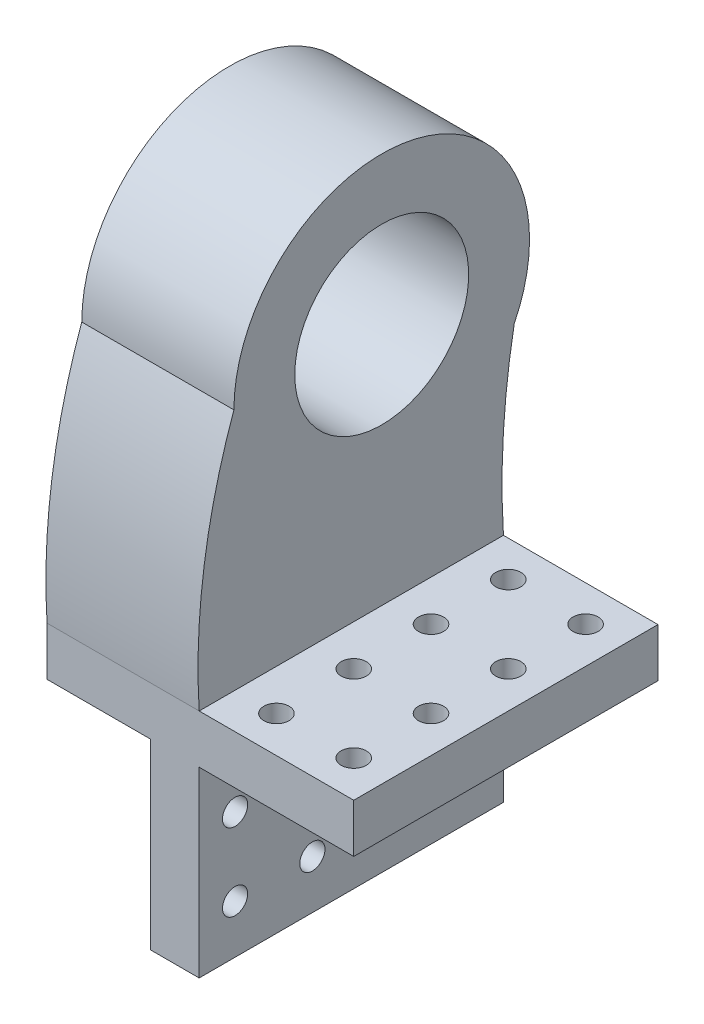
SolidWorks part; units mm, degrees
ref_plane "Alzado" through (0, 0, 0) normal (0, 0, 1) x (1, 0, 0)
ref_plane "Planta" through (0, 0, 0) normal (0, 1, 0) x (1, 0, 0)
ref_plane "Vista lateral" through (0, 0, 0) normal (1, 0, 0) x (0, 0, -1)
sketch "Croquis1" plane through (0, 0, 0) normal (0, 1, 0) x (1, 0, 0)
  line L1 (-25.2, -25) -> (25.2, -25)
  line L2 (-25.2, -25) -> (-25.2, 25)
  line L3 (-25.2, 25) -> (25.2, 25)
  line L4 (25.2, -25) -> (25.2, 25)
  line L5 (-25.2, -25) -> (25.2, 25) construction
  line L6 (-25.2, 25) -> (25.2, -25) construction
  point P0 (0, 0)
  dimension "D1" = 50.4
  dimension "D2" = 50
extrude "Saliente-Extruir1" add sketch "Croquis1" along normal blind 8
sketch "Croquis2" plane through (-25.2, 0, 0) normal (-1, 0, 0) x (0, 0, 1)
  line L0 (-25, 8) -> (25, 8) construction
  line L1 (25, 8) -> (25, 0) construction
  line L2 (-25, 8) -> (25, 8)
  circle A0 centre (-5, 48) radius 14.29
  arc A1 (19.29, 48) -> (-26.7814, 37.2494) centre (-5, 48) ccw
  arc A2 (-25, 8) -> (-26.7814, 37.2494) centre (-144.7726, 15.3844) ccw
  arc A3 (25, 8) -> (19.29, 48) centre (-74.8101, 14.1597) ccw
  dimension "D1" = 28.58
  dimension "D2" = 10
  dimension "D5" = 100
  dimension "D6" = 120
  dimension "D3" = 40
  dimension "D4" = 30
extrude "Saliente-Extruir2" add sketch "Croquis2" against normal blind 25
sketch "Croquis3" plane through (0, 0, 0) normal (0, -1, 0) x (1, 0, 0)
  line L1 (-8.2, -25) -> (-0.2, -25)
  line L2 (-8.2, -25) -> (-8.2, 25)
  line L3 (-8.2, 25) -> (-0.2, 25)
  line L4 (-0.2, -25) -> (-0.2, 25)
  line L5 (-25.2, 25) -> (25.2, 25) construction
  line L7 (25.2, 25) -> (25.2, -25) construction
  dimension "D1" = 8
  dimension "D2" = 25.4
extrude "Saliente-Extruir3" add sketch "Croquis3" along normal blind 30
sketch "Croquis4" plane through (0, 8, 0) normal (0, 1, 0) x (1, 0, 0)
  line L0 (25.2, -25) -> (25.2, 25) construction
  line L1 (-0.2, -25) -> (25.2, -25) construction
  circle A0 centre (19.2, -19) radius 2.07
  circle A1 centre (19.2, -6.3) radius 2.07
  circle A2 centre (19.2, 6.4) radius 2.07
  circle A3 centre (19.2, 19.1) radius 2.07
  circle A4 centre (6.5, 19.1) radius 2.07
  circle A5 centre (6.5, 6.4) radius 2.07
  circle A6 centre (6.5, -6.3) radius 2.07
  circle A7 centre (6.5, -19) radius 2.07
  dimension "D1" = 4.14
  dimension "D2" = 6
  dimension "D3" = 6
  dimension "D4" = 4
  dimension "D5" = 2
extrude "Cortar-Extruir1" cut sketch "Croquis4" against normal blind 30
sketch "Croquis5" plane through (-8.2, 0, 0) normal (-1, 0, 0) x (0, 0, 1)
  line L0 (25, -30) -> (-25, -30) construction
  line L1 (-25, -30) -> (-25, 0) construction
  circle A0 centre (-19, -22) radius 2.07
  circle A1 centre (-6.3, -22) radius 2.07
  circle A2 centre (6.4, -22) radius 2.07
  circle A3 centre (19.1, -22) radius 2.07
  circle A4 centre (-19, -9.3) radius 2.07
  circle A5 centre (-6.3, -9.3) radius 2.07
  circle A6 centre (6.4, -9.3) radius 2.07
  circle A7 centre (19.1, -9.3) radius 2.07
  dimension "D1" = 4.14
  dimension "D2" = 8
  dimension "D3" = 6
  dimension "D4" = 4
  dimension "D5" = 2
extrude "Cortar-Extruir2" cut sketch "Croquis5" against normal through all
